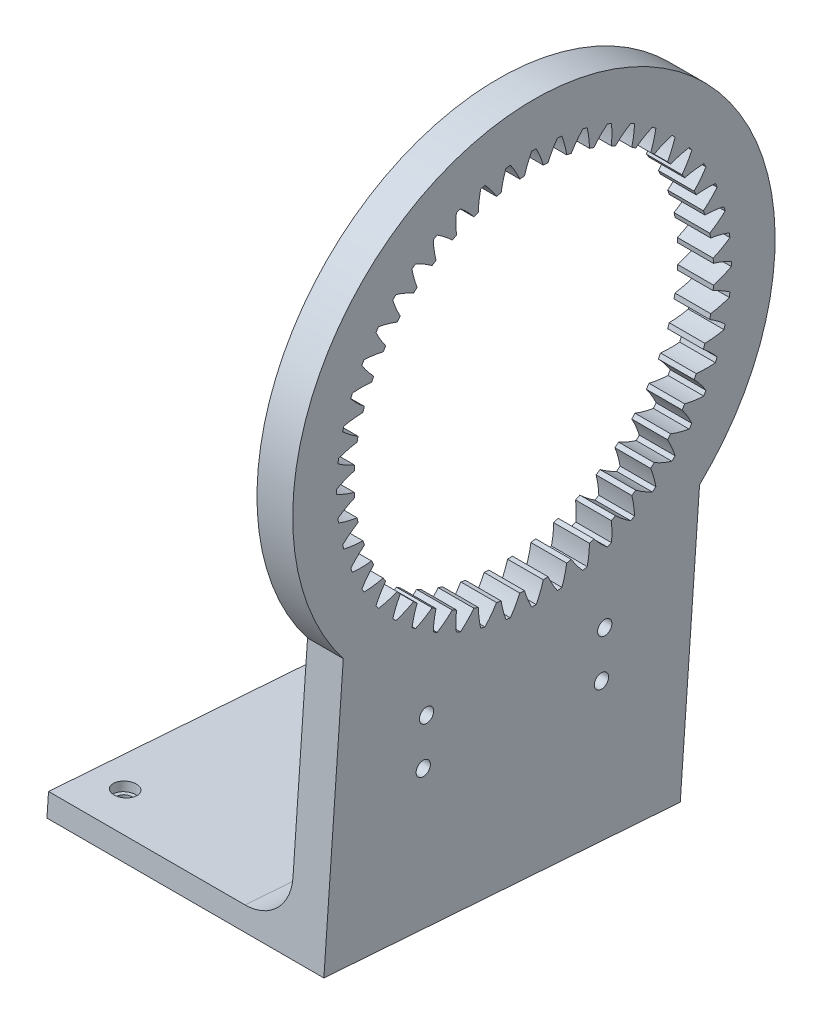
SolidWorks part; units mm, degrees
material "PLA personnalisé"
ref_plane "Plane1" through (0, 0, 0) normal (0, 0, 1) x (1, 0, 0)
ref_plane "Plane2" through (0, 0, 0) normal (0, 1, 0) x (1, 0, 0)
ref_plane "Plane3" through (0, 0, 0) normal (1, 0, 0) x (0, 0, -1)
other "Configuration Table"
sketch "HoldingSke" plane through (0, 0, 0) normal (0, 1, 0) x (1, 0, 0)
  line L0 (0, 0) -> (0.3824, -0.4247)
  line L1 (-15, 0) -> (100, 0) construction
  line L2 (0, 0) -> (-2.1039, 2.3779)
  line L3 (0, 0) -> (-11.863, 4.5341)
  line L4 (0, 0) -> (5.7786, 6.4178)
  line L5 (0, 0) -> (-23.7986, -8.8762)
  line L6 (0, 0) -> (-10.5278, -7.1032)
  line L7 (-2.1039, 2.3779) -> (3.3635, 27.1825)
  line L8 (-76.2, 4.1279) -> (-54.61, 4.1279)
  line L9 (-71.009, 38.7566) -> (-53.1078, 45.2721)
  line L10 (-76.2, 71.12) -> (104.1128, 71.12)
  line L11 (0, 0) -> (-8, 0)
  line L12 (-76.2, 101.6) -> (-76.147, 101.6)
  line L13 (24.9733, 27.94) -> (52.9518, 28.4284)
  line L14 (24.9733, 27.94) -> (24.9743, 27.94)
  line L15 (24.9733, 27.94) -> (100.4006, 29.5858)
  circle A0 centre (0, 0) radius 54
  circle A1 centre (0, 0) radius 12.7
  circle A2 centre (0, 0) radius 12.7
  dimension "Num_teeth" = 48
  dimension "Pitch_radius" = 180.3128
  dimension "Width" = 8
  dimension "Diameter" = 108
sketch "BasProSke" plane through (0, 0, 0) normal (0, 1, 0) x (1, 0, 0)
  line L0 (-10, 0) -> (60, 0) construction
  line L1 (0, 40.25) -> (0, 54)
  line L2 (0, 40.25) -> (8, 40.25)
  line L3 (8, 40.25) -> (8, 54)
  line L4 (8, 54) -> (0, 54)
  dimension "Thickness" = 8
  dimension "Diameter" = 108
revolve "Base-Revolve" add sketch "BasProSke" angle 360 about L0
sketch "TooCutSke" plane through (0, 0, 0) normal (1, 0, 0) x (0, 0, -1)
  line L3 (1.5067, 41.973) -> (1.5067, 53.6633) construction
  line L4 (0, 0) -> (0, 59.563) construction
  line L5 (0, 0) -> (-4.4688, 68.1812) construction
  line L6 (-18.0846, 34.4113) -> (35.4386, 37.9194) construction
  circle A0 centre (0, 0) radius 42 construction
  circle A1 centre (0, 0) radius 44.1885 construction
  circle A2 centre (0, 0) radius 35.5204 construction
  circle A3 centre (0, 0) radius 40.2246 construction
  arc A4 (2.1106, 40.1692) -> (0.502, 44.1856) centre (-18.0846, 34.4113) ccw
  arc A5 (2.1106, 40.1692) -> (-2.1106, 40.1692) centre (0, 0) ccw
  arc A6 (0.502, 44.1856) -> (-0.502, 44.1856) centre (0, 0) ccw
  arc A7 (-0.502, 44.1856) -> (-2.1106, 40.1692) centre (18.0846, 34.4113) ccw
extrude "ToothCut" cut sketch "TooCutSke" along normal through all
fillet "Breaks" [suppressed] radius 0.175
fillet "RootFillets" [suppressed] radius 0.4385
pattern_circular "TeethCuts" count 48 over 360 about axis through (-10, 0, 0) along (1, 0, 0) of "RootFillets", "Breaks", "ToothCut"
sketch "Esquisse1" plane through (8, 0, 0) normal (1, 0, 0) x (0, 0, -1)
  circle A0 centre (0, 0) radius 44.1885
  circle A1 centre (0, 0) radius 48.6885
  circle A2 centre (3.5329, 48.5602) radius 1.6
  dimension "D1" = 4.5
  dimension "D2" = 3.2
extrude "Enlèv. mat.-Extru.1" cut sketch "Esquisse1" against normal blind 10 contours A2
pattern_circular "Répétition circulaire1" count 6 over 360 about axis through (8, 0, 0) along (-1, 0, 0) of "Enlèv. mat.-Extru.1"
sketch "Esquisse2" plane through (8, 0, 0) normal (1, 0, 0) x (0, 0, -1)
  line L0 (-41.8261, -21.3656) -> (37.963, -27.1706) construction
  line L1 (-41.8261, -21.3656) -> (37.963, -27.1706)
  line L2 (-41.8261, -21.3656) -> (-47.0256, -92.8324)
  line L3 (37.963, -27.1706) -> (32.7635, -98.6374)
  line L4 (-47.0256, -92.8324) -> (32.7635, -98.6374)
  line L5 (0, 0) -> (-7.131, -95.7349) construction
  line L6 (-44.4258, -57.099) -> (-4.4748, -60.0748) construction
  line L7 (35.3633, -62.904) -> (-4.4748, -60.0748) construction
  circle A0 centre (0, 0) radius 54
  dimension "D1" = 96
  dimension "D2" = 80
extrude "Boss.-Extru.1" add sketch "Esquisse2" against normal through all contours A0 L2 L4 L3 region at (8, -71.7912, 5.4319)
sketch "Esquisse3" plane through (8, 0, 0) normal (1, 0, 0) x (0, 0, -1)
  circle A0 centre (-3.5329, -48.5602) radius 2.4787
extrude "Boss.-Extru.2" add sketch "Esquisse3" against normal blind 8
pattern_circular "Répétition circulaire3" count 6 over 360 about axis through (8, 0, 0) along (-1, 0, 0) of "Boss.-Extru.2"
sketch "Esquisse4" plane through (0, 0, 0) normal (-1, 0, 0) x (0, 0, 1)
  line L0 (7.131, -95.7349) -> (0, 0) construction
  line L1 (47.0256, -92.8324) -> (-32.7635, -98.6374) construction
  line L2 (44.0455, -51.8715) -> (-35.7336, -57.8141) construction
  line L3 (42.6786, -33.0838) -> (47.0256, -92.8324) construction
  line L4 (-37.084, -39.2527) -> (-32.7635, -98.6374) construction
  line L5 (-35.008, -67.7877) -> (44.7711, -61.8452) construction
  circle A0 centre (-15.8593, -56.3337) radius 1.6
  circle A1 centre (-15.1165, -66.3061) radius 1.6
  circle A2 centre (24.773, -63.3348) radius 1.6
  circle A3 centre (24.0302, -53.3624) radius 1.6
  dimension "D3" = 3.2
  dimension "D4" = 3.2
  dimension "D1" = 55
  dimension "D2" = 10
  dimension "D5" = 20
  dimension "D6" = 20
extrude "Enlèv. mat.-Extru.2" cut sketch "Esquisse4" against normal blind 10
sketch "Esquisse5" plane through (8, 0, 0) normal (1, 0, 0) x (0, 0, -1)
  line L0 (-47.0256, -92.8324) -> (32.7635, -98.6374)
  line L1 (32.7635, -98.6374) -> (33.1264, -93.6506)
  line L2 (37.084, -39.2527) -> (32.7635, -98.6374) construction
  line L3 (33.1264, -93.6506) -> (-46.6628, -87.8456)
  line L4 (-42.6786, -33.0838) -> (-47.0256, -92.8324) construction
  line L5 (-46.6628, -87.8456) -> (-47.0256, -92.8324)
  dimension "D1" = 5
extrude "Boss.-Extru.3" add sketch "Esquisse5" against normal blind 54 from offset 8 offset against normal yes
fillet "Congé1" radius 10 1 edges at (0, -90.7481, 6.7682)
sketch "Esquisse6" plane through (0, -90.7601, 6.6032) normal (0, 0.9974, -0.0726) x (1, 0, 0)
  line L0 (-54, -0.1655) -> (-140.1065, -0.1655) construction
  line L1 (-54, 39.8345) -> (-54, -40.1655) construction
  line L2 (-54, -0.1655) -> (-10, -0.1655) construction
  line L3 (-10, -40.1655) -> (-10, 39.8345) construction
  circle A0 centre (-64, -0.1655) radius 35
  circle A1 centre (-29, -0.1655) radius 2.5
  circle A2 centre (-46.5, -30.4764) radius 2.5
  circle A3 centre (-81.5, -30.4764) radius 2.5
  circle A4 centre (-99, -0.1655) radius 2.5
  circle A5 centre (-81.5, 30.1454) radius 2.5
  circle A6 centre (-46.5, 30.1454) radius 2.5
  point P23 (-64, -0.1655)
  dimension "D2" = 70
  dimension "D3" = 5
  dimension "D1" = 10
  dimension "D4" = 6
extrude "Enlèv. mat.-Extru.3" cut sketch "Esquisse6" against normal blind 2 contours A2 | A1 | A6
sketch "Esquisse7" plane through (0, -90.7601, 6.6032) normal (0, 0.9974, -0.0726) x (1, 0, 0)
  circle A0 centre (-29, -0.1655) radius 1.6
  circle A1 centre (-46.5, 30.1454) radius 1.6
  circle A2 centre (-46.5, -30.4764) radius 1.6
  dimension "D1" = 3.2
  dimension "D2" = 3.2
  dimension "D3" = 3.2
extrude "Enlèv. mat.-Extru.4" cut sketch "Esquisse7" against normal blind 5
equation "' \"Module@HoldingSke\" = 6.35"
equation "' \"Num_teeth@HoldingSke\" = 24"
equation "' \"Ap@HoldingSke\" =  14.5"
equation "' \"Ap@HoldingSke\" = 14.5"
equation "' \"Width@HoldingSke\" = 12"
equation "' \"Diameter@HoldingSke\" = 8 * 25.4"
equation "' \"Show_teeth@HoldingSke\" = 100"
equation "' \"Backlash@HoldingSke\" = 0.009 * 25.4"
equation "' \"Addendum_fac@HoldingSke\" = 1.0"
equation "' \"Dedendum_fac@HoldingSke\" = 1.25"
equation "' \"Dedendum_add@HoldingSke\" = 0.00005 * 25.4"
equation "' \"Clearance_fac@HoldingSke\" = 0.25"
equation "\"Pitch@HoldingSke\" = 1 / \"Module@HoldingSke\" "
equation "\"Overcut_dia@TooCutSke\" = (\"Num_teeth@HoldingSke\" - 2 * \"Addendum_fac@HoldingSke\") / \"Pitch@HoldingSke\" - 0.002 * 25.4"
equation "\"Pitch_dia@TooCutSke\" = \"Num_teeth@HoldingSke\" / \"Pitch@HoldingSke\""
equation "\"Base_dia@TooCutSke\" = \"Num_teeth@HoldingSke\" / \"Pitch@HoldingSke\" * cos((\"Ap@HoldingSke\"  * 3.14159265 / 180)) * 0.90"
equation "\"Root_dia@TooCutSke\" = \"Num_teeth@HoldingSke\"  / \"Pitch@HoldingSke\" + 2 *  \"Dedendum_fac@HoldingSke\"/ \"Pitch@HoldingSke\" + \"Dedendum_add@HoldingSke\" * 2"
equation "\"Half_ang@TooCutSke\" = 180 / \"Num_teeth@HoldingSke\""
equation "\"Half_CT@TooCutSke\" = \"Num_teeth@HoldingSke\" / \"Pitch@HoldingSke\" * sin((3.14159265 / 2 / \"Num_teeth@HoldingSke\")) / 2 + 10 * \"Backlash@HoldingSke\" / 4"
equation "\"Flank_rad@TooCutSke\" = \"Num_teeth@HoldingSke\" / \"Pitch@HoldingSke\" / 4"
equation "\"Radius@RootFillets\"= \"Clearance_fac@HoldingSke\" / \"Pitch@HoldingSke\" + \"Dedendum_add@HoldingSke\""
equation "\"Break_rad@Breaks\" = 0.02 / \"Pitch@HoldingSke\" * 5"
equation "\"Num_teeth@TeethCuts\" = int( \"Show_teeth@HoldingSke\" ) + 1"
equation "\"Num_teeth@TeethCuts\" = ((sgn( \"Num_teeth@TeethCuts\" - \"Num_teeth@HoldingSke\" )-1)*( \"Num_teeth@TeethCuts\" - \"Num_teeth@HoldingSke\" ))/-2+ \"Num_teeth@HoldingSke\""
equation "\"Num_teeth@TeethCuts\" = ((sgn( \"Num_teeth@TeethCuts\" - 2.0)+1)*( \"Num_teeth@TeethCuts\" - 2.0))/2 +2.0"
equation "\"Angle@TeethCuts\" = 360.0 / \"Num_teeth@HoldingSke\""
equation "\"Diameter@BasProSke\" = \"Num_teeth@HoldingSke\"  / \"Pitch@HoldingSke\" + 2 *  \"Dedendum_fac@HoldingSke\"/ \"Pitch@HoldingSke\" + \"Dedendum_add@HoldingSke\" * 2 + 0.002 * 25.4"
equation "\"Diameter@BasProSke\" = ((sgn( \"Diameter@BasProSke\"  - \"Diameter@HoldingSke\" )+1)*( \"Diameter@BasProSke\"  - \"Diameter@HoldingSke\" ))/2 + \"Diameter@HoldingSke\""
equation "\"Inside_diameter@BasProSke\" =  (\"Num_teeth@HoldingSke\" - 2 * \"Addendum_fac@HoldingSke\") / \"Pitch@HoldingSke\" "
equation "\"Thickness@BasProSke\"  = \"Width@HoldingSke\""
